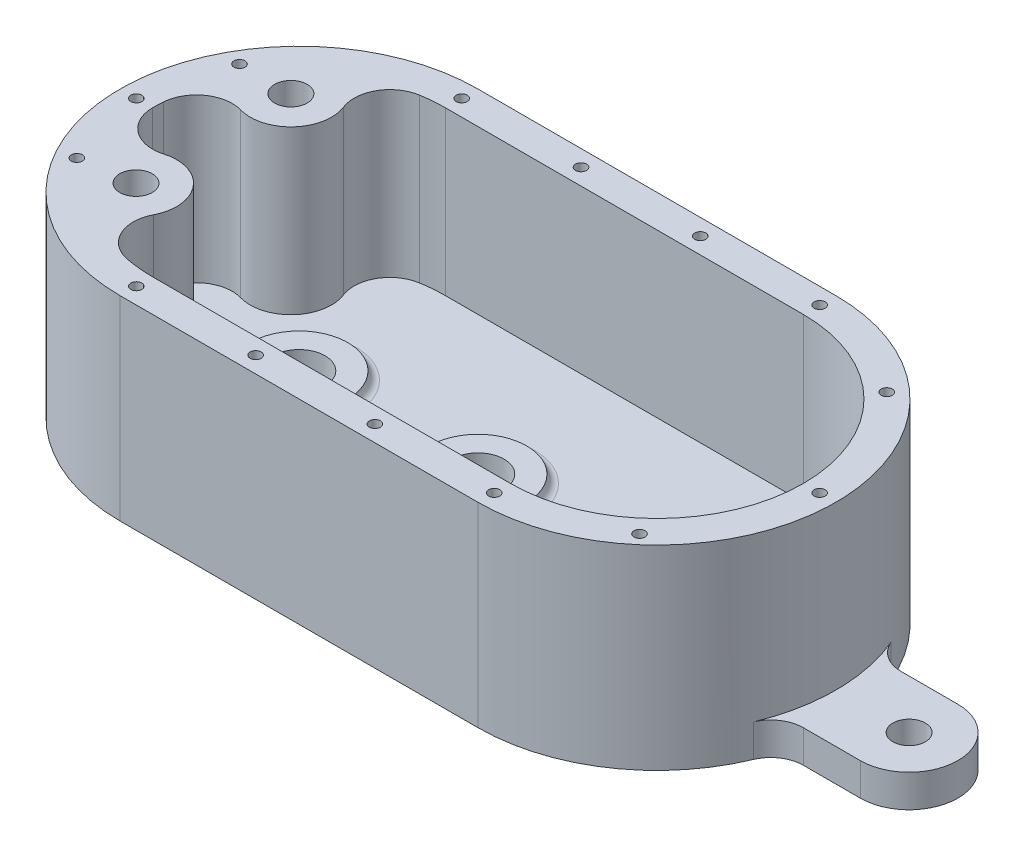
SolidWorks part; units mm, degrees
ref_plane "Plano frontal" through (0, 0, 0) normal (0, 0, 1) x (1, 0, 0)
ref_plane "Plano superior" through (0, 0, 0) normal (0, 1, 0) x (1, 0, 0)
ref_plane "Plano direito" through (0, 0, 0) normal (1, 0, 0) x (0, 0, -1)
sketch "Esboço2" plane through (0, 0, 0) normal (0, 1, 0) x (1, 0, 0)
  line L0 (-110, 110) -> (110, 110)
  line L1 (110, -110) -> (-110, -110)
  line L2 (-110, 90) -> (110, 90)
  line L3 (110, -90) -> (-110, -90)
  line L4 (265, -30) -> (230, -30)
  line L5 (265, 30) -> (230, 30)
  arc A0 (-110, 110) -> (-110, -110) centre (-110, 0) ccw
  arc A1 (110, -110) -> (110, 110) centre (110, 0) ccw
  circle A2 centre (-110, 0) radius 16
  circle A3 centre (-110, 0) radius 30
  circle A4 centre (0, 0) radius 16
  circle A5 centre (0, 0) radius 30
  circle A6 centre (110, 0) radius 16
  circle A7 centre (110, 0) radius 30
  arc A8 (-110, 90) -> (-124.8359, 88.7688) centre (-110, 0) ccw
  arc A9 (110, -90) -> (110, 90) centre (110, 0) ccw
  circle A10 centre (-165, 50) radius 10
  arc A11 (-171.8252, 25.9497) -> (-141.7071, 59.0797) centre (-165, 50) ccw
  arc A12 (-124.8359, 88.7688) -> (-141.7071, 59.0797) centre (-121.2093, 67.0697) ccw
  arc A13 (-171.8252, 25.9497) -> (-199.7691, 3.1308) centre (-177.8314, 4.7855) ccw
  circle A14 centre (-165, -45.2145) radius 10
  arc A15 (-142.7668, -56.6463) -> (-171.9149, -21.1899) centre (-165, -45.2145) ccw
  arc A16 (-199.7691, 3.1308) -> (-171.9149, -21.1899) centre (-178, -0.0482) ccw
  arc A17 (-142.7668, -56.6463) -> (-127.4727, -88.2876) centre (-123.2016, -66.7062) ccw
  arc A18 (-127.4727, -88.2876) -> (-110, -90) centre (-110, 0) ccw
  arc A19 (-199.7769, 6.3337) -> (-200, -0.0638) centre (-110, 0) ccw
  arc A20 (265, -30) -> (265, 30) centre (265, 0) ccw
  circle A21 centre (265, 0) radius 10
  arc A22 (230, -30) -> (211.5385, -42.3077) centre (230, -50) ccw
  arc A23 (211.5385, 42.3077) -> (230, 30) centre (230, 50) ccw
  point P32 (0, 0)
  dimension "D1" = 220
  dimension "D3" = 32
  dimension "D4" = 60
  dimension "D5" = 110
  dimension "D6" = 180
  dimension "D7" = 20
  dimension "D8" = 50
  dimension "D11" = 44
  dimension "D13" = 60
  dimension "D14" = 155
  dimension "D15" = 40
  dimension "D2" = 220
  dimension "D9" = 55
  dimension "D10" = 50
  dimension "D12" = 50
extrude "Ressalto-extrusão1" add sketch "Esboço2" along normal blind 20 contours A17 A18 L3 A9 L2 A8 A12 A11 A13 A16 A15 A3 A5 A7 region at (0, 0, -85.6137)
extrude "Ressalto-extrusão2" add sketch "Esboço2<3>" along normal blind 25 contours A3 A2 | A5 A4 | A7 A6 region at (-139.1515, 0, 0) region at (-29.1515, 0, 0) region at (80.8485, 0, 0)
sketch "Esboço2<3>" plane through (0, 0, 0) normal (0, 1, 0) x (1, 0, 0) same geometry as "Esboço2"
fillet "Filete1" radius 5 3 edges at (110, 20, 30) (0, 20, 30) (-110, 20, 30)
extrude "Ressalto-extrusão3" add sketch "Esboço2<4>" along normal blind 120 contours L1 A1 L0 A0 A19 A13 A11 A12 A8 L2 A9 L3 A18 A17 A15 A16 A14 A10 region at (0, 0, -105.0807)
sketch "Esboço2<4>" plane through (0, 0, 0) normal (0, 1, 0) x (1, 0, 0) same geometry as "Esboço2"
extrude "Ressalto-extrusão4" add sketch "Esboço2<5>" along normal blind 20 contours A23 A1 A22 L4 A20 L5 A21 region at (252.3854, 0, 0)
sketch "Esboço2<5>" plane through (0, 0, 0) normal (0, 1, 0) x (1, 0, 0) same geometry as "Esboço2"
hole_wizard "Broca de rosquear para tarraxa de M8x1.253" positions "Esboço15" profile "Esboço16" hole size "M8x1.25" standard "Ansi Metric"
sketch "Esboço15" plane through (0, 120, 0) normal (0, 1, 0) x (1, 0, 0)
  line L0 (-110, 100) -> (-36.6667, 100)
  line L1 (-36.6667, 100) -> (36.6667, 100)
  line L2 (36.6667, 100) -> (110, 100)
  line L4 (-110, -100) -> (-36.6667, -100)
  line L5 (-36.6667, -100) -> (36.6667, -100)
  line L6 (36.6667, -100) -> (110, -100)
  circle A0 centre (-110, 0) radius 16 construction
  circle A1 centre (-110, 0) radius 100
  circle A2 centre (110, 0) radius 100
  point P0 (-210, 0)
  point P2 (-196.6025, 50)
  point P4 (-196.6025, -50)
  point P6 (-110, 100)
  point P8 (-36.6667, 100)
  point P10 (36.6667, 100)
  point P12 (110, 100)
  point P14 (177.009, 74.228)
  point P16 (210, 0)
  point P18 (176.4799, -77.1889)
  point P20 (110, -100)
  point P22 (36.6667, -100)
  point P24 (-36.6667, -100)
  point P26 (-110, -100)
  dimension "D3" = 200
  dimension "D2" = 50
  dimension "D4" = 50
sketch "Esboço16" plane through (-210, 120, 0) normal (1, 0, 0) x (0, 0, 1)
  line L0 (0, 0) -> (0, 20.17)
  line L1 (0, 20.17) -> (3.4, 18.1271)
  line L2 (3.4, 18.1271) -> (3.4, 0)
  line L5 (3.4, 0) -> (0, 0)
  line L10 (0, 20.17) -> (-3.4, 18.1271) construction
  line L11 (0, -6.35) -> (0, 107.95) construction
  dimension "Hole Dia." = 6.8
  dimension "Hole Depth" = 20.17
  dimension "Drill Angle" = 118
hole_wizard "Broca de rosquear para tarraxa de M1.2x0.251" positions "Esboço17" profile "Esboço18" hole size "M1.2x0.25" standard "Ansi Metric"
sketch "Esboço17" plane through (0, 120, 0) normal (0, 1, 0) x (1, 0, 0)
  point P0 (-196.6025, 50)
  point P3 (-210, 0)
  point P6 (-196.6025, -50)
  point P9 (-110, -100)
  point P12 (-110, 100)
  point P15 (-36.6667, 100)
  point P18 (36.6667, 100)
  point P21 (-36.6667, -100)
  point P24 (36.6667, -100)
  point P27 (110, 100)
  point P30 (177.009, 74.228)
  point P33 (210, 0)
  point P36 (176.4799, -77.1889)
  point P39 (110, -100)
sketch "Esboço18" plane through (-196.6025, 120, -50) normal (1, 0, 0) x (0, 0, 1)
  line L0 (0, 0) -> (0, 30)
  line L1 (0, 30) -> (3.4, 27.9571)
  line L2 (3.4, 27.9571) -> (3.4, 0)
  line L5 (3.4, 0) -> (0, 0)
  line L10 (0, 30) -> (-3.4, 27.9571) construction
  line L11 (0, -6.35) -> (0, 107.95) construction
  dimension "Hole Dia." = 6.8
  dimension "Hole Depth" = 30
  dimension "Drill Angle" = 118
